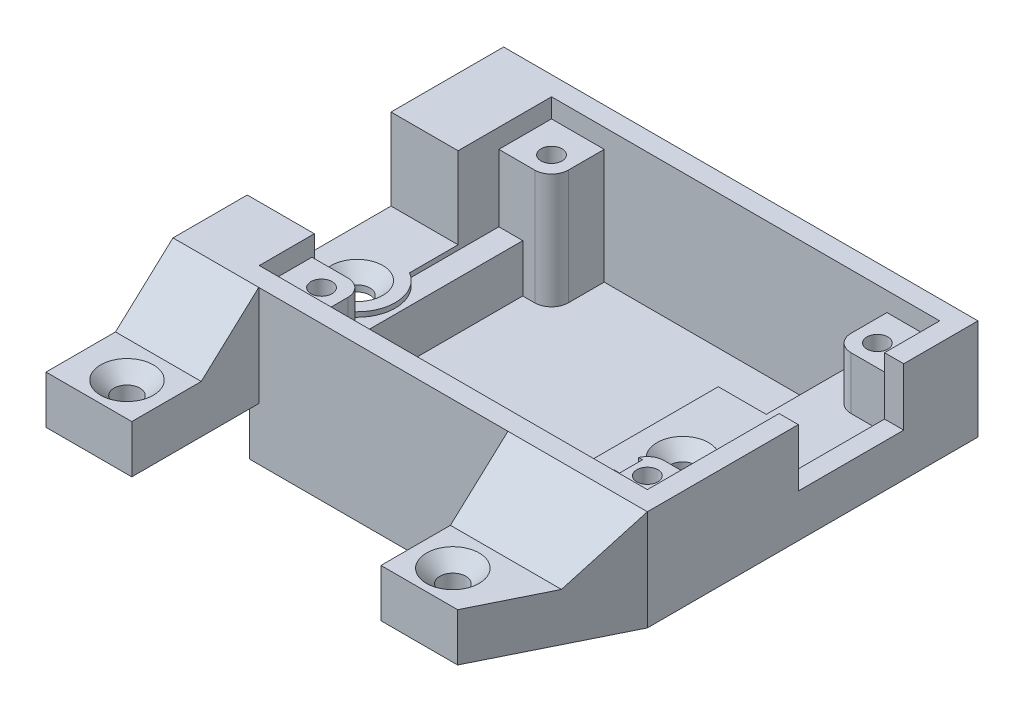
SolidWorks part; units mm, degrees
note: The reader was unsure of these and kept them because the rebuilt part matched: shared geometry of "草图18<3>".
material "PLA"
ref_plane "前视基准面" through (0, 0, 0) normal (0, 0, 1) x (1, 0, 0)
ref_plane "上视基准面" through (0, 0, 0) normal (0, 1, 0) x (1, 0, 0)
ref_plane "右视基准面" through (0, 0, 0) normal (1, 0, 0) x (0, 0, -1)
sketch "草图1" plane through (0, 0, 0) normal (0, 1, 0) x (1, 0, 0)
  line L1 (-22.25, -17.25) -> (22.25, -17.25)
  line L2 (-22.25, -17.25) -> (-22.25, 17.25)
  line L3 (-22.25, 17.25) -> (22.25, 17.25)
  line L4 (22.25, -17.25) -> (22.25, 17.25)
  line L5 (0, 17.25) -> (0, -17.25) construction
  line L6 (-22.25, 0) -> (22.25, 0) construction
  point P0 (0, 0)
  dimension "D1" = 44.5
  dimension "D2" = 34.5
extrude "凸台-拉伸1" add sketch "草图1" along normal blind 16
shell "抽壳1" thickness 2 removed face at (0, 16, 0)
sketch "草图4" plane through (0, 2, 0) normal (0, 1, 0) x (1, 0, 0)
  line L0 (-20.25, 15.25) -> (-20.25, -15.25) construction
  line L1 (-17.25, -8.75) -> (-12.25, -8.75) construction
  line L2 (-17.25, -8.75) -> (-17.25, 8.75) construction
  line L3 (-17.25, 8.75) -> (-12.25, 8.75) construction
  line L4 (-12.25, -8.75) -> (-12.25, 8.75) construction
  line L5 (-14.75, 8.75) -> (-14.75, -8.75) construction
  line L6 (-17.25, 0) -> (-12.25, 0) construction
  line L12 (-11.25, 9.75) -> (-11.25, -2.25)
  line L13 (-12.25, 8.75) -> (-14.75, 8.75) construction
  line L17 (-12.25, 8.75) -> (-12.25, -1.25) construction
  line L18 (-12.25, -1.25) -> (-14.75, -1.25) construction
  line L19 (-14.75, 8.75) -> (-14.75, -1.25) construction
  line L20 (-13.5, -1.25) -> (-13.5, 8.75) construction
  line L21 (-12.25, 3.75) -> (-14.75, 3.75) construction
  line L22 (-11.25, -2.25) -> (-15.75, -2.25)
  line L23 (-15.75, 9.75) -> (-15.75, -2.25)
  line L24 (-11.25, 9.75) -> (-15.75, 9.75)
  point P200 (-13.5, 3.75)
  dimension "D1" = 17.5
  dimension "D2" = 5
  dimension "D3" = 3
  dimension "D4" = 10
  dimension "D5" = 1
extrude "切除-拉伸2" [suppressed] cut sketch "草图4" against normal through all and the other way through all
sketch "草图2" plane through (0, 2, 0) normal (0, 1, 0) x (1, 0, 0)
  line L0 (20.25, -15.25) -> (20.25, -9.75)
  line L5 (20.25, 0) -> (0, 0) construction
  line L6 (20.25, -15.25) -> (20.25, 15.25) construction
  line L7 (0, 0) -> (0, -15.25) construction
  line L8 (-20.25, 15.25) -> (-14.75, 15.25)
  line L9 (-20.25, 15.25) -> (-20.25, 9.75)
  line L10 (-20.25, 9.75) -> (-14.75, 9.75)
  line L11 (-14.75, 15.25) -> (-14.75, 9.75)
  line L12 (-17.5, 9.75) -> (-17.5, 15.25) construction
  line L13 (-20.25, 12.5) -> (-14.75, 12.5) construction
  line L14 (-20.25, -15.25) -> (20.25, -15.25) construction
  line L15 (-20.25, -9.75) -> (-14.75, -9.75)
  line L16 (-14.75, -15.25) -> (-14.75, -9.75)
  line L17 (-20.25, -15.25) -> (-14.75, -15.25)
  line L18 (-20.25, -15.25) -> (-20.25, -9.75)
  line L19 (20.25, -15.25) -> (14.75, -15.25)
  line L20 (14.75, -15.25) -> (14.75, -9.75)
  line L21 (20.25, -9.75) -> (14.75, -9.75)
  line L22 (20.25, 9.75) -> (14.75, 9.75)
  line L23 (14.75, 15.25) -> (14.75, 9.75)
  line L24 (20.25, 15.25) -> (14.75, 15.25)
  line L25 (20.25, 15.25) -> (20.25, 9.75)
  point P194 (-17.5, 12.5)
  dimension "D1" = 5.5
extrude "凸台-拉伸2" add sketch "草图2" along normal blind 12
sketch "草图3" plane through (0, 14, 0) normal (0, 1, 0) x (1, 0, 0)
  line L1 (-17, -12) -> (17, -12) construction
  line L2 (-17, -12) -> (-17, 12) construction
  line L3 (-17, 12) -> (17, 12) construction
  line L4 (17, -12) -> (17, 12) construction
  line L5 (0, 12) -> (0, -12) construction
  line L6 (-17, 0) -> (17, 0) construction
  circle A0 centre (-17, 12) radius 1.1
  circle A1 centre (17, 12) radius 1.1
  circle A2 centre (17, -12) radius 1.1
  circle A3 centre (-17, -12) radius 1.1
  point P0 (0, 0)
  dimension "D3" = 2.2
  dimension "D1" = 34
  dimension "D2" = 24
extrude "切除-拉伸1" cut sketch "草图3" against normal through all
fillet "圆角1" radius 1.75 4 edges at (14.75, 8, -9.75) (14.75, 8, 9.75) (-14.75, 8, -9.75) (-14.75, 8, 9.75)
sketch "草图5" [suppressed] plane through (0, 0, 0) normal (0, -1, 0) x (1, 0, 0)
  line L0 (-11.25, -3.75) -> (-15.75, -3.75) construction
  line L1 (-11.25, 2.25) -> (-11.25, -9.75) construction
  line L2 (-15.75, -9.75) -> (-15.75, 2.25) construction
  line L4 (-8.25, -8) -> (-11.25, -8)
  line L5 (-8.25, -8) -> (-8.25, 0.5)
  line L6 (-8.25, 0.5) -> (-11.25, 0.5)
  line L7 (-11.25, -8) -> (-11.25, 0.5)
  line L8 (-9.75, 0.5) -> (-9.75, -8) construction
  line L9 (-8.25, -3.75) -> (-11.25, -3.75) construction
  point P6 (-9.75, -3.75)
  dimension "D1" = 8.5
  dimension "D2" = 3
extrude "切除-拉伸3" [suppressed] cut sketch "草图5" against normal through all
sketch "草图7" plane through (0, 0, 0) normal (0, -1, 0) x (1, 0, 0)
  line L0 (7.15, -17.25) -> (7.15, 17.25)
  line L1 (22.25, -17.25) -> (-22.25, -17.25) construction
  line L2 (-22.25, 17.25) -> (22.25, 17.25) construction
  line L3 (7.15, 17.25) -> (22.25, 17.25)
  line L4 (22.25, 17.25) -> (22.25, -17.25) construction
  line L5 (22.25, 17.25) -> (22.25, -17.25)
  line L6 (22.25, -17.25) -> (7.15, -17.25)
  line L7 (22.25, -17.25) -> (-22.25, -17.25) construction
  line L8 (-22.25, 17.25) -> (-17.75, 17.25)
  line L9 (-22.25, 17.25) -> (-22.25, -17.25)
  line L10 (-22.25, -17.25) -> (-17.75, -17.25)
  line L11 (-17.75, 17.25) -> (-17.75, -17.25)
  dimension "D1" = 24.9
  dimension "D2" = 4.5
extrude "切除-拉伸4" cut sketch "草图7" against normal blind 7
sketch "草图8" plane through (0, 7, 0) normal (0, -1, 0) x (1, 0, 0)
  line L0 (7.15, -17.25) -> (22.25, -17.25)
  line L1 (7.15, -17.25) -> (7.15, 17.25)
  line L2 (7.15, 17.25) -> (22.25, 17.25)
  line L3 (22.25, -17.25) -> (22.25, 17.25) construction
  line L4 (22.25, -17.25) -> (22.25, 17.25)
  line L6 (-22.25, 17.25) -> (-17.75, 17.25)
  line L7 (-22.25, 17.25) -> (-22.25, -17.25)
  line L8 (-22.25, -17.25) -> (-17.75, -17.25)
  line L9 (-17.75, 17.25) -> (-17.75, -17.25)
  circle A4 centre (17, 12) radius 1.1 construction
  circle A5 centre (17, -12) radius 1.1 construction
  circle A6 centre (17, 12) radius 1.1
  circle A7 centre (17, -12) radius 1.1
extrude "凸台-拉伸3" add sketch "草图8" along normal blind 1.5
sketch "草图9" plane through (7.15, 0, 0) normal (1, 0, 0) x (0, 0, -1)
  line L1 (17.25, 0) -> (-17.25, 0)
  line L2 (17.25, 0) -> (17.25, 5.5)
  line L3 (17.25, 5.5) -> (-17.25, 5.5)
  line L4 (-17.25, 0) -> (-17.25, 5.5)
extrude "凸台-拉伸4" add sketch "草图9" along normal blind 1.5
sketch "草图12" plane through (22.25, 0, 0) normal (1, 0, 0) x (0, 0, -1)
  line L0 (4, 16) -> (4, 10) construction
  line L1 (9.5, 10) -> (-1.5, 10)
  line L2 (9.5, 10) -> (9.5, 16)
  line L3 (9.5, 16) -> (-1.5, 16)
  line L4 (-1.5, 10) -> (-1.5, 16)
  line L5 (-17.25, 16) -> (17.25, 16) construction
  line L6 (-17.25, 16) -> (17.25, 16) construction
  line L7 (-10.9, 14) -> (-13.1, 14) construction
  line L8 (-10.9, 14) -> (-13.1, 14) construction
  line L9 (-12, 14) -> (-12, 9.7215) construction
  dimension "D1" = 11
  dimension "D2" = 6
  dimension "D3" = 16
extrude "切除-拉伸6" cut sketch "草图12" against normal blind 5
sketch "草图13" plane through (-17.75, 0, 0) normal (-1, 0, 0) x (0, 0, 1)
  line L0 (17.25, 0) -> (-17.25, 0)
  line L9 (-17.25, 0) -> (-17.25, 5.5)
  line L10 (-17.25, 5.5) -> (17.25, 5.5)
  line L11 (17.25, 5.5) -> (17.25, 0) construction
  line L12 (12.8047, 5.5) -> (17.25, 5.5) construction
  line L13 (17.25, 5.5) -> (17.25, 0)
extrude "凸台-拉伸7" add sketch "草图13" along normal blind 1.5
sketch "草图14" plane through (0, 0, 0) normal (0, -1, 0) x (1, 0, 0)
  circle A0 centre (-17, 12) radius 1.1
  circle A1 centre (-17, -12) radius 1.1
  arc A2 (-17.75, -12.8047) -> (-17.75, -11.1953) centre (-17, -12) ccw construction
  arc A3 (-17.75, 11.1953) -> (-17.75, 12.8047) centre (-17, 12) ccw construction
extrude "切除-拉伸7" cut sketch "草图14" against normal through all
sketch "草图16" plane through (0, 5.5, 0) normal (0, -1, 0) x (1, 0, 0)
  line L0 (-22.25, 17.25) -> (-27.25, 17.25)
  line L1 (-27.25, 17.25) -> (-27.25, -17.25)
  line L2 (-27.25, -17.25) -> (-22.25, -17.25)
  line L3 (-22.25, -17.25) -> (-22.25, 17.25)
  dimension "D1" = 5
extrude "凸台-拉伸8" add sketch "草图16" against normal up to surface (10.5 mm away) up to face at (7.0833, 16, -1.3333)
sketch "草图18" plane through (0, 5.5, 0) normal (0, -1, 0) x (1, 0, 0)
  line L1 (-18.3, 30.5) -> (-26.3, 30.5)
  line L5 (11.7, 20.0701) -> (11.7, 30.5) construction
  line L7 (15.7, 17.25) -> (15.7, 30.5) construction
  line L8 (15.7, 30.5) -> (7.7, 30.5)
  line L10 (-22.3, 20.0701) -> (-22.3, 30.5) construction
  line L13 (-18.3, 17.25) -> (-27.25, 17.25)
  line L15 (15.7, 30.5) -> (15.7, 17.25)
  line L16 (15.7, 17.25) -> (7.7, 17.25)
  line L17 (-27.25, 17.25) -> (-27.25, 30.5)
  line L18 (-27.25, 30.5) -> (-26.3, 30.5)
  line L21 (-18.3, 30.5) -> (-18.3, 17.25)
  line L24 (7.7, 30.5) -> (7.7, 17.25)
  line L25 (22.25, 17.25) -> (8.65, 17.25) construction
  circle A2 centre (11.7, 27) radius 1.35
  circle A3 centre (-22.3, 27) radius 1.35
  circle A4 centre (-22.3, 3) radius 1.35
  circle A5 centre (11.7, 3) radius 1.35
  circle A6 centre (-17, 12) radius 1.1 construction
  dimension "D5" = 2.7
  dimension "D3" = 5.3
  dimension "D1" = 34
  dimension "D2" = 24
  dimension "D4" = 3.5
  dimension "D7" = 9
  dimension "D9" = 4
extrude "凸台-拉伸9" add sketch "草图18" against normal blind 5
extrude "切除-拉伸8" cut sketch "草图18<3>" against normal through all and the other way through all contours A4 | A5
sketch "草图18<3>" plane through (0, 5.5, 0) normal (0, -1, 0) x (1, 0, 0) same geometry as "草图18"
hole_wizard "M2.5 锥坑高头螺钉的锥形沉头孔1" positions "3D草图1" profile "草图19" countersink size "M2.5" standard "ISO"
sketch3d "3D草图1"
  line L0 (-22.3, 10.5, 27) -> (-22.3, 5.5, 27) construction
  line L2 (11.7, 10.5, 27) -> (11.7, 5.5, 27) construction
  point P0 (-22.3, 10.5, 27)
  point P8 (11.7, 10.5, 27)
sketch "草图19" plane through (-22.3, 10.5, 27) normal (1, 0, 0) x (0, 0, 1)
  line L0 (0, 0) -> (0, 25.6412)
  line L1 (0, 25.6412) -> (1.35, 24.83)
  line L2 (1.35, 24.83) -> (1.35, 1.4)
  line L3 (1.35, 1.4) -> (2.75, 0)
  line L5 (2.75, 0) -> (0, 0)
  line L6 (-1.35, 1.4) -> (-2.75, 0) construction
  line L10 (0, 25.6412) -> (-1.35, 24.83) construction
  line L11 (0, -6.35) -> (0, 107.95) construction
  dimension "孔直径" = 2.7
  dimension "孔深度" = 24.83
  dimension "近端锥形沉头孔直径" = 5.5
  dimension "近端锥形沉头孔角度" = 90
  dimension "导头角度" = 118
sketch "草图20" plane through (-18.3, 0, 0) normal (1, 0, 0) x (0, 0, -1)
  line L0 (-23.25, 10.5) -> (-17.25, 10.5)
  line L1 (-30.5, 10.5) -> (-17.25, 10.5) construction
  line L2 (-17.25, 10.5) -> (-17.25, 16)
  line L3 (-17.25, 16) -> (-23.25, 10.5)
  dimension "D1" = 6
extrude "凸台-拉伸10" add sketch "草图20" along direction (-1, 0, 0) on the side against the normal up to surface (8.95 mm away) up to face at (-27.25, 10.6667, 10.1667)
sketch "草图22" plane through (0, 14, 0) normal (0, 1, 0) x (1, 0, 0)
  line L0 (15.3, -13.2) -> (15.3, -10.8)
  line L2 (15.3, -13.2) -> (13.3, -13.2)
  line L3 (13.3, -13.2) -> (13.3, -10.8)
  line L4 (13.3, -10.8) -> (15.3, -10.8)
  circle A0 centre (17, -12) radius 1.1 construction
  dimension "D1" = 1.2
  dimension "D3" = 1.7
  dimension "D2" = 1.2
  dimension "D4" = 2
extrude "切除-拉伸9" cut sketch "草图22" against normal blind 1
hole_wizard "打孔尺寸(%根据十字)槽沉头木螺钉的类型1" positions "3D草图2" profile "草图23" countersink size "M2" standard "GB" end condition through all
sketch3d "3D草图2"
  line L0 (-17, 0, 12) -> (-17, 14, 12) construction
  line L1 (-17, 0, -12) -> (-17, 14, -12) construction
  point P0 (-17, 0, 12)
  point P4 (-17, 0, -12)
sketch "草图23" plane through (-17, 0, 12) normal (1, 0, 0) x (0, 0, -1)
  line L0 (0, 0) -> (0, 16)
  line L1 (0, 16) -> (1.1, 16)
  line L2 (1.1, 16) -> (1.1, 1.15)
  line L3 (1.1, 1.15) -> (2.25, 0)
  line L5 (2.25, 0) -> (0, 0)
  line L6 (-1.1, 1.15) -> (-2.25, 0) construction
  line L11 (0, -6.35) -> (0, 107.95) construction
  dimension "通孔孔直径" = 2.2
  dimension "通孔孔深度" = 16
  dimension "近端锥形沉头孔直径" = 4.5
  dimension "近端锥形沉头孔角度" = 90
sketch "草图25" plane through (0, 7, 0) normal (0, 1, 0) x (1, 0, 0)
  line L0 (7.15, 3.25) -> (12.15, 3.25)
  line L1 (7.15, -15.25) -> (7.15, 15.25) construction
  line L2 (12.15, 3.25) -> (12.15, 15.25)
  line L3 (14.75, 15.25) -> (7.15, 15.25) construction
  line L4 (12.15, 15.25) -> (7.15, 15.25)
  line L5 (7.15, 15.25) -> (7.15, 3.25)
  dimension "D1" = 12
  dimension "D2" = 5
extrude "切除-拉伸10" cut sketch "草图25" against normal through all
sketch "草图26" plane through (0, 0, -3.25) normal (0, 0, -1) x (-1, 0, 0)
  line L0 (-7.15, 7) -> (-12.15, 7)
  line L1 (-12.15, 7) -> (-12.15, 0)
  line L2 (-12.15, 0) -> (-7.15, 0)
  line L3 (-7.15, 0) -> (-7.15, 7)
extrude "凸台-拉伸11" add sketch "草图26" along normal blind 2
sketch "草图27" plane through (0, 0, -17.25) normal (0, 0, -1) x (-1, 0, 0)
  line L0 (-12.15, 0) -> (-8.65, 0)
  line L1 (-8.65, 0) -> (-8.65, 5.5)
  line L2 (-8.65, 5.5) -> (-12.15, 5.5)
  line L3 (-12.15, 5.5) -> (-12.15, 0)
extrude "凸台-拉伸12" add sketch "草图27" against normal up to surface (2 mm away)
sketch "草图28" plane through (12.15, 0, 0) normal (1, 0, 0) x (0, 0, -1)
  line L0 (17.25, 0) -> (17.25, 5.5)
  line L1 (17.25, 5.5) -> (3.25, 5.5)
  line L2 (3.25, 5.5) -> (3.25, 0)
  line L3 (3.25, 0) -> (17.25, 0)
extrude "凸台-拉伸13" add sketch "草图28" along normal blind 2
sketch "草图29" plane through (0, 0, 0) normal (0, -1, 0) x (1, 0, 0)
  line L0 (12.15, -5.25) -> (7.15, -5.25) construction
  line L1 (12.15, -5.25) -> (12.15, -15.25) construction
  line L2 (12.15, -15.25) -> (7.15, -15.25) construction
  line L3 (7.15, -15.25) -> (7.15, -5.25) construction
  line L4 (12.15, -5.25) -> (7.15, -5.25)
  line L5 (12.15, -5.25) -> (12.15, -15.25)
  line L6 (12.15, -15.25) -> (7.15, -15.25)
  line L7 (7.15, -15.25) -> (7.15, -5.25)
extrude "凸台-拉伸14" add sketch "草图29" against normal up to surface (2 mm away) up to face at (-9.575, 2, -0.4773)
sketch "草图31" plane through (-27.25, 0, 0) normal (-1, 0, 0) x (0, 0, 1)
  line L0 (-17.25, 16) -> (17.25, 16) construction
  line L1 (9.5, 7.5) -> (-5.5, 7.5)
  line L2 (9.5, 7.5) -> (9.5, 16)
  line L3 (9.5, 16) -> (-5.5, 16)
  line L4 (-5.5, 7.5) -> (-5.5, 16)
  line L5 (2, 16) -> (2, 7.5) construction
  line L6 (9.5, 11.75) -> (-5.5, 11.75) construction
  line L7 (13.1, 14) -> (10.9, 14) construction
  line L8 (13.1, 14) -> (10.9, 14) construction
  line L9 (12, 14) -> (12, 9.3137) construction
  point P0 (2, 11.75)
  dimension "D1" = 8.5
  dimension "D2" = 15
  dimension "D3" = 10
extrude "切除-拉伸11" cut sketch "草图31" against normal blind 10
sketch "草图32" plane through (0, 7, 0) normal (0, 1, 0) x (1, 0, 0)
  line L10 (12.15, 15.25) -> (12.15, 5.25)
  line L11 (12.15, 5.25) -> (7.15, 5.25)
  line L12 (7.15, 5.25) -> (7.15, -15.25)
  line L13 (7.15, -15.25) -> (14.75, -15.25)
  line L14 (14.75, -15.25) -> (14.75, -11.5)
  line L15 (16.5, -9.75) -> (20.25, -9.75)
  line L16 (20.25, -9.75) -> (20.25, 9.75)
  line L17 (20.25, 9.75) -> (16.5, 9.75)
  line L18 (14.75, 11.5) -> (14.75, 15.25)
  line L19 (14.75, 15.25) -> (12.15, 15.25)
  line L20 (12.15, 15.25) -> (12.15, 5.25)
  line L21 (12.15, 5.25) -> (7.15, 5.25)
  line L22 (7.15, 5.25) -> (7.15, -15.25)
  line L23 (7.15, -15.25) -> (14.75, -15.25)
  line L24 (14.75, -15.25) -> (14.75, -11.5)
  line L25 (16.5, -9.75) -> (20.25, -9.75)
  line L26 (20.25, -9.75) -> (20.25, 9.75)
  line L27 (20.25, 9.75) -> (16.5, 9.75)
  line L28 (14.75, 11.5) -> (14.75, 15.25)
  line L29 (14.75, 15.25) -> (12.15, 15.25)
  circle A0 centre (11.7, -3) radius 1.35 construction
  circle A1 centre (11.7, -3) radius 1.35
  arc A2 (16.5, -9.75) -> (14.75, -11.5) centre (16.5, -11.5) ccw
  arc A3 (14.75, 11.5) -> (16.5, 9.75) centre (16.5, 11.5) ccw
  arc A4 (16.5, -9.75) -> (14.75, -11.5) centre (16.5, -11.5) ccw
  arc A5 (14.75, 11.5) -> (16.5, 9.75) centre (16.5, 11.5) ccw
  dimension "D1" = 0
extrude "凸台-拉伸15" add sketch "草图32" along normal blind 1.5
sketch "草图34" plane through (0, 7.5, 0) normal (0, 1, 0) x (1, 0, 0)
  circle A0 centre (-22.3, -3) radius 1.35 construction
  circle A1 centre (-22.3, -3) radius 1.35
  circle A2 centre (-22.3, -3) radius 4
  dimension "D1" = 8
extrude "凸台-拉伸18" add sketch "草图34" against normal up to surface (0.5 mm away) up to face at (-19, 7, 0)
hole_wizard "打孔尺寸(%根据十字)槽沉头木螺钉的类型2" positions "3D草图3" profile "草图33" countersink size "M2.5" standard "GB" end condition through all
sketch3d "3D草图3"
  line L0 (11.7, 8.5, 3) -> (11.7, 5.5, 3) construction
  line L2 (-22.3, 7.5, 3) -> (-22.3, 5.5, 3) construction
  point P0 (11.7, 8.5, 3)
  point P11 (-22.3, 7.5, 3)
sketch "草图33" plane through (11.7, 8.5, 3) normal (1, 0, 0) x (0, 0, 1)
  line L0 (0, 0) -> (0, 8.5)
  line L1 (0, 8.5) -> (1.35, 8.5)
  line L2 (1.35, 8.5) -> (1.35, 1.35)
  line L3 (1.35, 1.35) -> (2.7, 0)
  line L5 (2.7, 0) -> (0, 0)
  line L6 (-1.35, 1.35) -> (-2.7, 0) construction
  line L11 (0, -6.35) -> (0, 107.95) construction
  dimension "通孔孔直径" = 2.7
  dimension "通孔孔深度" = 8.5
  dimension "近端锥形沉头孔直径" = 5.4
  dimension "近端锥形沉头孔角度" = 90
sketch "草图35" plane through (0, 10.5, 0) normal (0, 1, 0) x (1, 0, 0)
  line L0 (15.7, -30.5) -> (15.7, -17.25)
  line L1 (15.7, -17.25) -> (22.25, -17.25)
  line L2 (-18.3, -17.25) -> (22.25, -17.25) construction
  line L3 (22.25, -17.25) -> (15.7, -30.5)
extrude "凸台-拉伸19" add sketch "草图35" against normal up to surface (5 mm away) up to face at (11.7, 5.5, 25.65)
sketch "草图36" plane through (7.7, 0, 0) normal (-1, 0, 0) x (0, 0, 1)
  line L0 (17.25, 10.5) -> (23.25, 10.5)
  line L1 (30.5, 10.5) -> (17.25, 10.5) construction
  line L2 (23.25, 10.5) -> (17.25, 16)
  line L3 (17.25, 16) -> (17.25, 10.5)
extrude "凸台-拉伸20" add sketch "草图36" against normal blind 17.5
sketch "草图37" plane through (0, 16, 0) normal (0, 1, 0) x (1, 0, 0)
  line L0 (15.7, -30.5) -> (22.25, -17.25)
  line L1 (22.25, -17.25) -> (25.2, -17.25)
  line L2 (25.2, -17.25) -> (25.2, -30.8248)
  line L3 (25.2, -30.8248) -> (15.7, -30.5)
extrude "切除-拉伸12" cut sketch "草图37" against normal blind 17.5
